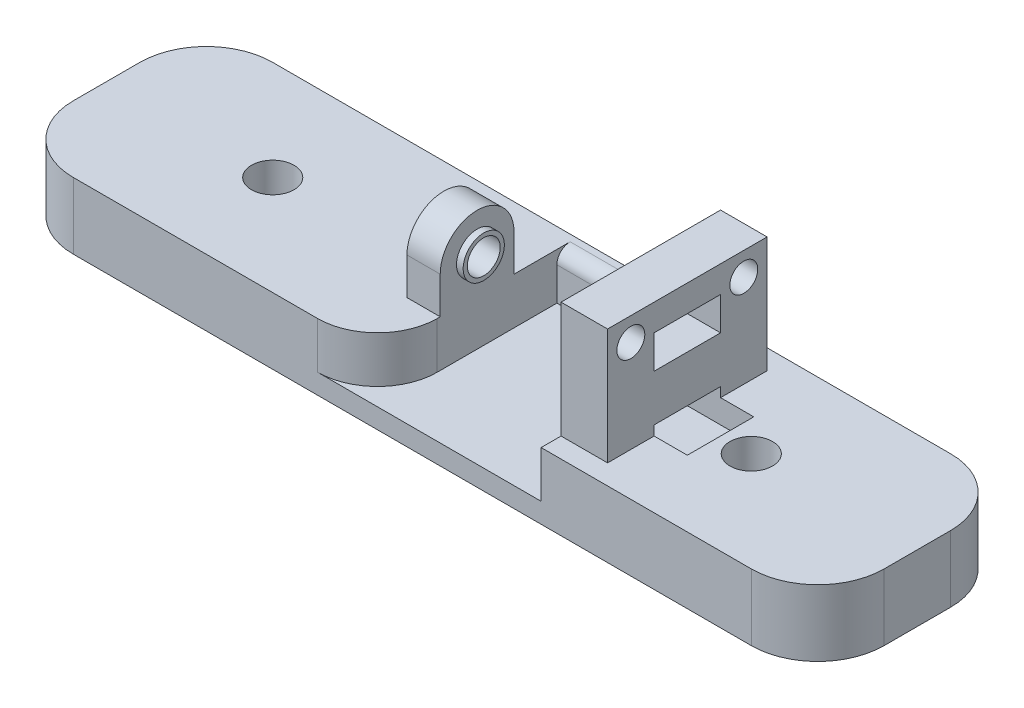
SolidWorks part; units mm, degrees
ref_plane "Front Plane" through (0, 0, 0) normal (0, 0, 1) x (1, 0, 0)
ref_plane "Top Plane" through (0, 0, 0) normal (0, 1, 0) x (1, 0, 0)
ref_plane "Right Plane" through (0, 0, 0) normal (1, 0, 0) x (0, 0, -1)
sketch "Sketch1" plane through (0, 0, 0) normal (0, 1, 0) x (1, 0, 0)
  line L1 (-61, 15) -> (61, 15)
  line L2 (-61, 15) -> (-61, -15)
  line L3 (-61, -15) -> (61, -15)
  line L4 (61, 15) -> (61, -15)
  line L5 (-61, 15) -> (61, -15) construction
  line L6 (-61, -15) -> (61, 15) construction
  point P0 (0, 0)
  dimension "D1" = 122
  dimension "D2" = 30
extrude "Boss-Extrude1" add sketch "Sketch1" along normal blind 10
ref_plane "Plane1" through (0, 0, 0) normal (1, 0, 0) x (0, 0, -1)
ref_plane "Plane2" through (19.38, 0, 0) normal (1, 0, 0) x (0, 0, -1)
ref_plane "Plane3" through (-5.25, 0, 0) normal (1, 0, 0) x (0, 0, -1)
sketch "Sketch2" plane through (19.38, 0, 0) normal (1, 0, 0) x (0, 0, -1)
  line L0 (-15, 10) -> (15, 10) construction
  line L5 (-12, 10) -> (12, 10)
  line L6 (-12, 10) -> (-12, 27.4478)
  line L7 (-12, 27.4478) -> (12, 27.4478)
  line L8 (12, 10) -> (12, 27.4478)
  point P7 (0, 27.4478)
  dimension "D1" = 24
  dimension "D2" = 17.4478
extrude "Boss-Extrude2" add sketch "Sketch2" along normal blind 7
sketch "Sketch3" plane through (-5.25, 0, 0) normal (1, 0, 0) x (0, 0, -1)
  line L0 (-5.5522, 15.5522) -> (-5.5522, 10)
  line L1 (-15, 10) -> (15, 10) construction
  line L3 (-5.5522, 10) -> (5.5522, 10)
  line L4 (5.5522, 10) -> (5.5522, 15.5522)
  circle A0 centre (0, 15.5522) radius 2.475
  arc A1 (5.5522, 15.5522) -> (-5.5522, 15.5522) centre (0, 15.5522) ccw
  point P3 (0, 0)
  point P8 (0, 0)
  dimension "D1" = 4.95
  dimension "D2" = 5.5522
extrude "Boss-Extrude3" add sketch "Sketch3" against normal blind 5
sketch "Sketch4" plane through (0, 10, 0) normal (0, 1, 0) x (1, 0, 0)
  line L0 (-61, -15) -> (61, -15) construction
  line L1 (-5.25, 12) -> (19.38, 12)
  line L2 (-5.25, 12) -> (-5.25, -15)
  line L3 (-5.25, -15) -> (19.38, -15)
  line L4 (19.38, 12) -> (19.38, -15)
  line L5 (19.38, -12) -> (19.38, 12) construction
  point P0 (-5.25, 5.5522)
  dimension "D1" = 27
extrude "Cut-Extrude1" cut sketch "Sketch4" against normal blind 7
fillet "Fillet1" radius 10 4 edges at (-61, 5, -15) (-61, 5, 15) (61, 5, -15) (61, 5, 15)
sketch "Sketch7" plane through (0, 10, 0) normal (0, 1, 0) x (1, 0, 0)
  line L0 (-61, 5) -> (-61, -5) construction
  line L1 (0, 0) -> (0, 29.2953) construction
  circle A0 centre (-36, 0) radius 3.2
  circle A1 centre (36, 0) radius 3.2
  point P2 (-61, 0)
  dimension "D1" = 6.4
  dimension "D2" = 25
extrude "Cut-Extrude2" cut sketch "Sketch7" against normal through all
sketch "Sketch8" plane through (-5.25, 0, 0) normal (1, 0, 0) x (0, 0, -1)
  circle A0 centre (0, 15.5522) radius 2.475
  circle A1 centre (0, 15.5522) radius 3.1
  dimension "D1" = 4.95
  dimension "D2" = 6.2
extrude "Boss-Extrude5" add sketch "Sketch8" along normal blind 1
fillet "Fillet2" radius 9 1 edges at (-5.25, 6.5, 15)
fillet "Fillet3" radius 2 1 edges at (7.065, 10, -12)
sketch "Sketch9" plane through (19.38, 0, 0) normal (-1, 0, 0) x (0, 0, 1)
  line L0 (12, 27.4478) -> (12, 10) construction
  line L1 (-12, 27.4478) -> (12, 27.4478) construction
  line L2 (-12, 27.4478) -> (-12, 3.4478) construction
  line L3 (-12, 3.4478) -> (12, 3.4478) construction
  line L4 (12, 27.4478) -> (12, 3.4478) construction
  line L5 (-12, 27.4478) -> (12, 3.4478) construction
  line L6 (-12, 3.4478) -> (12, 27.4478) construction
  circle A0 centre (8.5, 23.9478) radius 2.1
  circle A1 centre (8.5, 6.9478) radius 2.1
  circle A2 centre (-8.5, 6.9478) radius 2.1
  circle A3 centre (-8.5, 23.9478) radius 2.1
  point P7 (0, 15.4478)
  dimension "D2" = 8.5
  dimension "D3" = 4.2
  dimension "D1" = 24
  dimension "D4" = 4
extrude "Cut-Extrude3" cut sketch "Sketch9" against normal blind 8
sketch "Sketch10" plane through (19.38, 0, 0) normal (-1, 0, 0) x (0, 0, 1)
  line L1 (-5, 23.4478) -> (5, 23.4478)
  line L2 (-5, 23.4478) -> (-5, 18.4478)
  line L3 (-5, 18.4478) -> (5, 18.4478)
  line L4 (5, 23.4478) -> (5, 18.4478)
  line L5 (-5, 23.4478) -> (5, 18.4478) construction
  line L6 (-5, 18.4478) -> (5, 23.4478) construction
  line L7 (-5, 11.4478) -> (5, 11.4478)
  line L8 (-5, 11.4478) -> (-5, 6.4478)
  line L9 (-5, 6.4478) -> (5, 6.4478)
  line L10 (5, 11.4478) -> (5, 6.4478)
  line L11 (-5, 11.4478) -> (5, 6.4478) construction
  line L12 (-5, 6.4478) -> (5, 11.4478) construction
  line L13 (-8.5, 23.9478) -> (8.5, 23.9478) construction
  point P0 (0, 20.9478)
  point P5 (0, 8.9478)
  point P10 (0, 23.9478)
  dimension "D1" = 5
  dimension "D2" = 3
  dimension "D3" = 10
  dimension "D4" = 12
extrude "Cut-Extrude4" cut sketch "Sketch10" against normal blind 12
